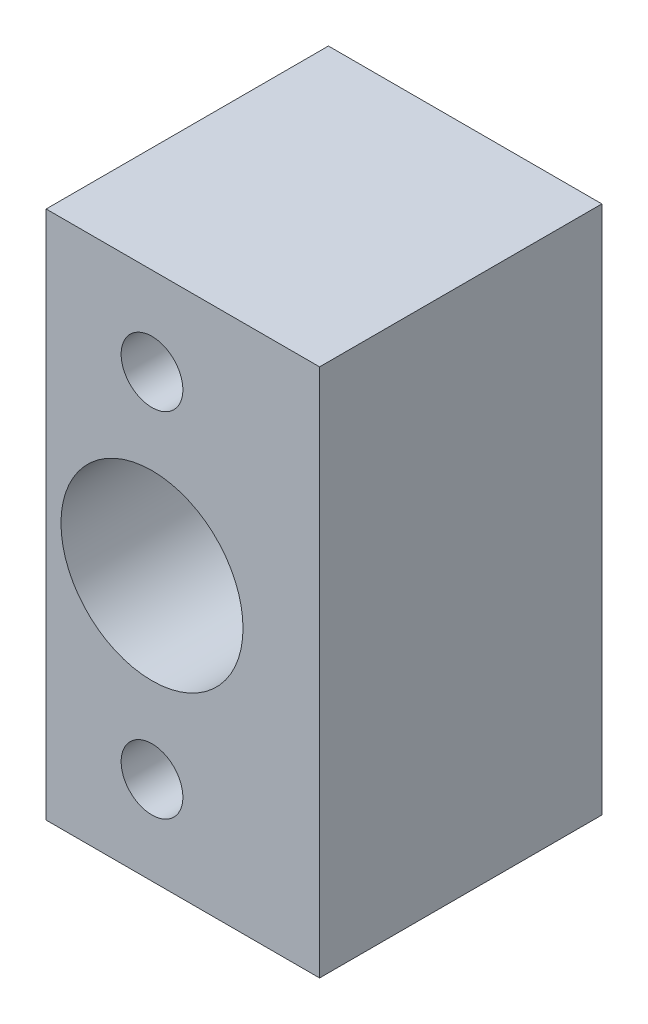
SolidWorks part; units mm, degrees
material "6061-T4 (SS)"
ref_plane "Front Plane" through (0, 0, 0) normal (0, 0, 1) x (1, 0, 0)
ref_plane "Top Plane" through (0, 0, 0) normal (0, 1, 0) x (1, 0, 0)
ref_plane "Right Plane" through (0, 0, 0) normal (1, 0, 0) x (0, 0, -1)
sketch "Sketch1" plane through (0, 0, 0) normal (0, 0, 1) x (1, 0, 0)
  line L5 (-6, 6) -> (0, 0) construction
  line L6 (0, 0) -> (6, 6) construction
  line L7 (9.5, 15) -> (-9.5, 15)
  line L8 (9.5, 15) -> (9.5, -15)
  line L9 (9.5, -15) -> (-9.5, -15)
  line L10 (-9.5, 15) -> (-9.5, -15)
  line L11 (9.5, 15) -> (-9.5, -15) construction
  line L12 (9.5, -15) -> (-9.5, 15) construction
  point P0 (0, 0)
  point P3 (0, 0)
  dimension "D1" = 19
  dimension "D4" = 30
extrude "Boss-Extrude1" add sketch "Sketch1" along normal blind 18
sketch "Sketch2" plane through (0, 0, 18) normal (0, 0, 1) x (1, 0, 0)
  circle A0 centre (0, 0) radius 5.1594
  dimension "D1" = 10.3187
extrude "Cut-Extrude1" cut sketch "Sketch2" against normal blind 11.5 contours A0
sketch "Sketch4" plane through (0, 0, 6.5) normal (0, 0, 1) x (1, 0, 0)
  circle A0 centre (0, 0) radius 4.8
  dimension "D1" = 9.6
extrude "Cut-Extrude3" cut sketch "Sketch4" against normal blind 0.5
sketch "Sketch5" plane through (0, 0, 6) normal (0, 0, 1) x (1, 0, 0)
  circle A0 centre (0, 0) radius 2.3813
  dimension "D1" = 4.7625
extrude "Cut-Extrude4" cut sketch "Sketch5" against normal blind 8 and the other way through all
sketch "Sketch6" plane through (0, 0, 0) normal (0, 0, 1) x (1, 0, 0)
  line L0 (-6, 15) -> (-6, -15)
  line L3 (9.5, 15) -> (-9.5, 15) construction
  line L4 (-9.5, -15) -> (9.5, -15) construction
  circle A0 centre (0, 0) radius 5.1594 construction
  point P6 (-6, 0)
  dimension "D1" = 6
extrude "Cut-Extrude6" cut sketch "Sketch6" against normal through all and the other way through all flip side to cut
sketch "Sketch11" plane through (0, 0, 0) normal (0, 0, -1) x (-1, 0, 0)
  line L1 (6, 15) -> (-9.5, 15)
  line L2 (6, 15) -> (6, -15)
  line L3 (6, -15) -> (-9.5, -15)
  line L4 (-9.5, 15) -> (-9.5, -15)
extrude "Boss-Extrude5" add sketch "Sketch11" along normal blind 5
sketch "Sketch12" plane through (0, 0, -5) normal (0, 0, -1) x (-1, 0, 0)
  circle A0 centre (0, 0) radius 4
  dimension "D1" = 8
extrude "Cut-Extrude8" cut sketch "Sketch12" against normal blind 7.5
sketch "Sketch13" plane through (0, 0, -5) normal (0, 0, -1) x (-1, 0, 0)
  line L2 (6, 15) -> (-9.5, 15) construction
  line L3 (0, 15) -> (0, -15) construction
  line L4 (-9.5, -15) -> (6, -15) construction
  circle A1 centre (0, -10) radius 1.75
  circle A2 centre (0, 10) radius 1.75
  point P0 (0, 5)
  point P4 (0, -5)
  point P6 (0, 0)
  dimension "D3" = 3.5
  dimension "D4" = 10
  dimension "D1" = 5
  dimension "D2" = 5
extrude "Cut-Extrude9" cut sketch "Sketch13" against normal through all
sketch "Sketch15" plane through (0, -15, 0) normal (0, -1, 0) x (1, 0, 0)
  line L1 (-6, -5) -> (9.5, -5) construction
  line L2 (-6, -5) -> (-6, 16) construction
  line L3 (-6, 16) -> (9.5, 16)
  line L4 (9.5, -5) -> (9.5, 16) construction
  line L5 (9.5, 18) -> (9.5, -5) construction
  line L6 (-6, 16) -> (9.5, 16)
  line L7 (-6, 16) -> (-6, 17) construction
  line L8 (-6, 17) -> (9.5, 17) construction
  line L9 (9.5, 16) -> (9.5, 17) construction
  line L10 (-6, -5) -> (9.5, -5)
  line L11 (-6, 18) -> (9.5, 18)
  line L12 (-6, 18) -> (-6, 16)
  line L13 (-6, 16) -> (9.5, 16)
  line L14 (9.5, 18) -> (9.5, 16)
  line L15 (-6, -5) -> (-6, 0)
  line L16 (-6, 0) -> (9.5, 0)
  line L17 (9.5, -5) -> (9.5, 0)
  line M5 (9.5, 18) -> (-6, 18)
  line M6 (-6, 18) -> (-6, -5)
  line M8 (9.5, -5) -> (9.5, 18)
  dimension "D1" = 21
  dimension "D2" = 1
  dimension "D3" = 5
extrude "Cut-Extrude11" cut sketch "Sketch15" against normal blind 41 contours L3 M6 M8 M5 | L15 L10 L17 L16 region at (1.75, -15, 17)
ref_axis "Axis1" through (-6, -15, 0) along (0.4148, 0.8029, 0.4282)
ref_plane "Plane2" through (-6, -15, 0) normal (0.4148, 0.8029, 0.4282) x (0.9099, -0.366, -0.1952)
sketch "Sketch17" plane through (-6, -15, 0) normal (0.4148, 0.8029, 0.4282) x (0.9099, -0.366, -0.1952)
  circle A0 centre (0, 0) radius 5
  point P2 (0, 0)
  point P3 (0, 0)
  point P4 (0, 0)
  dimension "D1" = 10
extrude "Cut-Extrude12" cut sketch "Sketch17" along normal blind 2
sketch "Sketch18" plane through (-5.1983, -10.0612, -5.366) normal (-0.4148, -0.8029, -0.4282) x (0.9088, -0.3427, -0.2379)
  point P0 (-0.3126, 7.052)
sketch "Sketch20" plane through (0, 0, 0) normal (0, 0, -1) x (-1, 0, 0)
  circle A0 centre (0, 10) radius 3.81
  circle A1 centre (0, -10) radius 3.81
  circle A3 centre (0, -10) radius 1.75 construction
  circle A4 centre (0, 10) radius 1.75 construction
  point P5 (0, 0)
  point P8 (0, 0)
  dimension "D1" = 7.62
extrude "Cut-Extrude13" cut sketch "Sketch20" against normal blind 4
